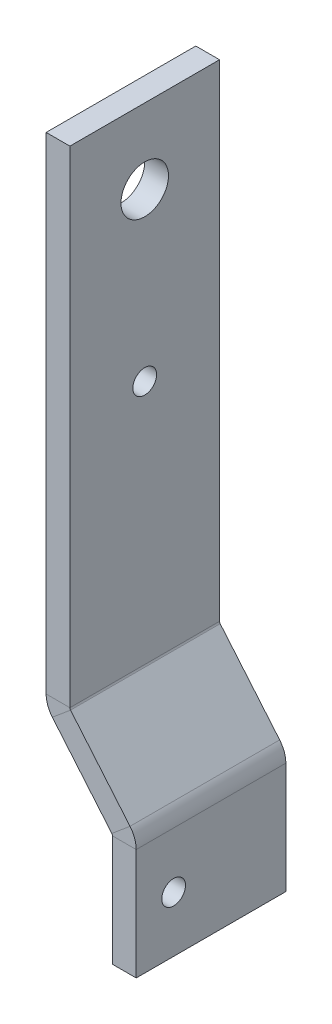
SolidWorks part; units mm, degrees
note: The reader was unsure of these and kept them because the rebuilt part matched: flange length of "Edge-Flange1", "Edge-Flange2".
ref_plane "Front Plane" through (0, 0, 0) normal (0, 0, 1) x (1, 0, 0)
ref_plane "Top Plane" through (0, 0, 0) normal (0, 1, 0) x (1, 0, 0)
ref_plane "Right Plane" through (0, 0, 0) normal (1, 0, 0) x (0, 0, -1)
sketch "Sketch1" plane through (0, 0, 0) normal (1, 0, 0) x (0, 0, -1)
  line L0 (0, 0) -> (40, 0)
  line L1 (40, 0) -> (40, -130)
  line L2 (40, -130) -> (0, -130)
  line L3 (0, -130) -> (0, 0)
  line L4 (20, 0) -> (20, -130) construction
  circle A0 centre (20, -20) radius 6.35
  circle A1 centre (20, -64.45) radius 3.175
  dimension "D3" = 12.7
  dimension "D4" = 6.35
  dimension "D1" = 40
  dimension "D2" = 130
  dimension "D5" = 20
  dimension "D6" = 44.45
base flange "Base-Flange1" sketch "Sketch1" thickness 6.35 reverse thickness direction no parameters "D1"=0.7366
edge flange "Edge-Flange1" sketch "Sketch10" flange angle 140 flange length 25 flange position bend outside bend radius 0.7366 thickness 6.35 relief rectangular parameters "D6"=10
sketch "Sketch10" plane through (0, -130, 0) normal (-0.766, -0.6428, 0) x (0, 0, -1)
  line L2 (0, 0) -> (0, 25)
  line L3 (0, 25) -> (40, 25)
  line L4 (40, 25) -> (40, 0)
  line L15 (0, 0) -> (40, 0) construction
  line L16 (0, 0) -> (40, 0)
bend "EdgeBend1" bend radius 0.7366 bend angle 40 parameters "D5"=1
edge flange "Edge-Flange2" sketch "Sketch13" flange angle 140 flange length 30 flange position bend outside bend radius 0.7366 thickness 6.35 relief rectangular parameters "D6"=10
sketch "Sketch13" plane through (11.2053, -153.5009, 0) normal (1, 0, 0) x (0, 0, 1)
  line L0 (-40, 0) -> (0, 0) construction
  line L1 (-40, 0) -> (0, 0)
  line L2 (-40, 0) -> (-40, 30)
  line L3 (-40, 30) -> (0, 30)
  line L4 (0, 30) -> (0, 0)
bend "EdgeBend2" bend radius 0.7366 bend angle 40 parameters "D5"=2
sketch "Sketch20" plane through (17.7276, 0, 0) normal (1, 0, 0) x (0, 0, -1)
  line L0 (20, -153.9744) -> (20, -183.7063) construction
  line L3 (0, -168.8403) -> (20, -168.8403) construction
  line L6 (0, -153.9744) -> (40, -153.9744) construction
  line L7 (0, -183.7063) -> (40, -183.7063) construction
  line L9 (0, -153.9744) -> (0, -183.7063) construction
  circle A1 centre (10, -168.8403) radius 3.175
  point P12 (10, -168.8403)
  dimension "D1" = 6.35
extrude "Cut-Extrude3" cut sketch "Sketch20" against normal up to surface (6.35 mm away) normal cut yes up to face at (11.3776, -168.8403, -20)
sketch "Bend-Lines1" [suppressed] plane through (0, 0, 0) normal (0, 1, 0) x (1, 0, 0)
sketch "Bounding-Box1" [suppressed] plane through (0, 0, 0) normal (0, 1, 0) x (1, 0, 0)
sheet metal parameters "Sheet-Metal1" thickness 6.35 parameters "D1"=0.7366
flat pattern "Flat-Pattern1" [suppressed]
sketch "Bend-Lines2" plane through (0, 0, 0) normal (0, 1, 0) x (1, 0, 0)
sketch3d "Bounding-Box2" [suppressed]
  line L0 (0, 0, 0) -> (0, -100, 0) construction
  line L1 (40, 0, 0) -> (40, -100, 0) construction
  line L2 (0, 0, 0) -> (40, 0, 0) construction
  line L3 (0, -100, 0) -> (40, -100, 0) construction
sheet metal parameters "Sheet-Metal2" thickness 6.35 parameters "D1"=0.7366
flat pattern "Flat-Pattern1" [suppressed]
sketch "Bend-Lines2" plane through (0, 0, 0) normal (1, 0, 0) x (0, 0, -1)
  line L0 (0, -131.0241) -> (40, -131.0241) construction
  line L1 (0, -131.0241) -> (40, -131.0241) construction
sketch3d "Bounding-Box2" [suppressed]
  line L0 (0, 0, 0) -> (0, -170.1493, 0) construction
  line L1 (40, 0, 0) -> (40, -170.1493, 0) construction
  line L2 (0, 0, 0) -> (40, 0, 0) construction
  line L3 (0, -170.1493, 0) -> (40, -170.1493, 0) construction
bend of the flat pattern "EdgeBend1>1"
sketch "Sketch16-2" plane through (0, -19.0965, 0) normal (1, 0, 0) x (0, 0, -1)
  line L0 (0, -132.0022) -> (40, -132.0022) construction
  circle A0 centre (20, -132.0022) radius 3.175
  dimension "D1" = 6.35
sheet metal parameters "Sheet-Metal3" thickness 6.35 parameters "D1"=0.7366
flat pattern "Flat-Pattern1" [suppressed]
sketch "Bend-Lines2" plane through (0, 0, 0) normal (1, 0, 0) x (0, 0, -1)
  line L0 (0, -131.3654) -> (40, -131.3654) construction
  line L1 (0, -131.3654) -> (40, -131.3654) construction
  line L2 (0, -151.5169) -> (40, -151.5169) construction
  line L3 (0, -151.5169) -> (40, -151.5169) construction
sketch3d "Bounding-Box2" [suppressed]
  line L0 (0, 0, 0) -> (0, -175.622, 0) construction
  line L1 (40, 0, 0) -> (40, -175.622, 0) construction
  line L2 (0, 0, 0) -> (40, 0, 0) construction
  line L3 (0, -175.622, 0) -> (40, -175.622, 0) construction
bend of the flat pattern "EdgeBend1>1"
bend of the flat pattern "EdgeBend2>1"
sheet metal parameters "Sheet-Metal6" thickness 6.35 parameters "D1"=0.7366
flat pattern "Flat-Pattern1"
sketch "Bend-Lines2" plane through (0, 0, 0) normal (1, 0, 0) x (0, 0, -1)
  line L0 (0, -131.3654) -> (40, -131.3654) construction
  line L1 (0, -131.3654) -> (40, -131.3654) construction
  line L2 (0, -158.8281) -> (40, -158.8281) construction
  line L3 (0, -158.8281) -> (40, -158.8281) construction
sketch3d "Bounding-Box2" [suppressed]
  line L0 (0, 0, 0) -> (0, -189.9254, 0) construction
  line L1 (40, 0, 0) -> (40, -189.9254, 0) construction
  line L2 (0, 0, 0) -> (40, 0, 0) construction
  line L3 (0, -189.9254, 0) -> (40, -189.9254, 0) construction
bend of the flat pattern "EdgeBend1>1"
bend of the flat pattern "EdgeBend2>1"
